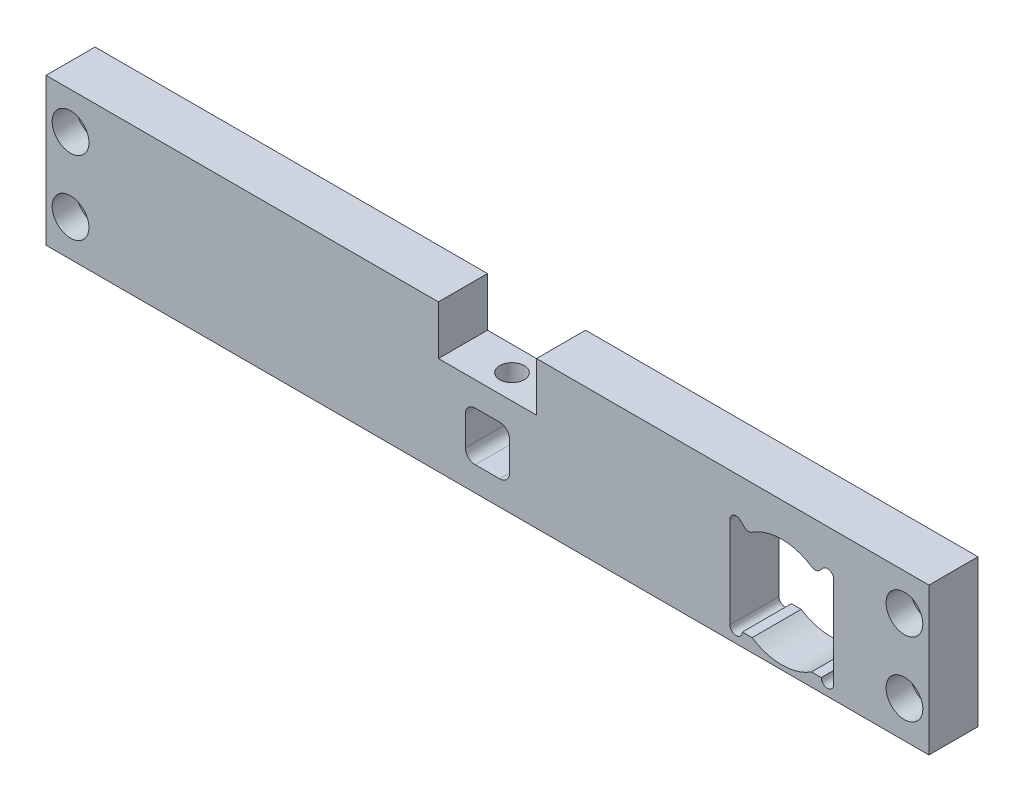
SolidWorks part; units mm, degrees
material "6061-T6 (SS)"
ref_plane "Front Plane" through (0, 0, 0) normal (0, 0, 1) x (1, 0, 0)
ref_plane "Top Plane" through (0, 0, 0) normal (0, 1, 0) x (1, 0, 0)
ref_plane "Right Plane" through (0, 0, 0) normal (1, 0, 0) x (0, 0, -1)
sketch "Sketch1" plane through (0, 0, 0) normal (0, 0, 1) x (1, 0, 0)
  line L1 (-190.5, -19.05) -> (38.1, -19.05)
  line L2 (-190.5, -19.05) -> (-190.5, 19.05)
  line L3 (-190.5, 19.05) -> (38.1, 19.05)
  line L4 (38.1, -19.05) -> (38.1, 19.05)
  line L5 (-190.5, -19.05) -> (38.1, 19.05) construction
  line L6 (-190.5, 19.05) -> (38.1, -19.05) construction
  line L7 (-190.5, 19.05) -> (38.1, 19.05)
  line L8 (-190.5, 19.05) -> (-190.5, -19.05)
  line L11 (-190.5, -19.05) -> (38.1, -19.05)
  line L12 (-190.5, -19.05) -> (-190.5, 19.05)
  line L15 (38.1, -19.05) -> (-190.5, -19.05)
  line L16 (38.1, -19.05) -> (38.1, 19.05)
  line L20 (38.1, -19.05) -> (38.1, 19.05)
  point P0 (0, 0)
  point P14 (-76.2, 0)
  dimension "D1" = 38.1
  dimension "D2" = 228.6
  dimension "D3" = 38.1
extrude "Boss-Extrude1" add sketch "Sketch1" along normal blind 12.7 contours L4 L3 L2 L1 region at (-76.2, 0, 0)
sketch "Sketch5" plane through (0, 0, 12.7) normal (0, 0, 1) x (1, 0, 0)
  line L0 (0, -3.81) -> (11.8187, 8.0087) construction
  line L1 (0, -3.81) -> (11.8187, -3.81) construction
  line L2 (0, -3.81) -> (0, 8.0087) construction
  line L3 (0, 8.0087) -> (11.8187, 8.0087) construction
  line L4 (11.8187, -3.81) -> (11.8187, 8.0087) construction
  line L5 (-10.6872, 9.1402) -> (-8.7721, 7.2252)
  line L6 (0, -3.81) -> (11.8187, -3.81) construction
  line L7 (0, -3.81) -> (0, -15.6287) construction
  line L8 (0, -15.6287) -> (11.8187, -15.6287) construction
  line L9 (11.8187, -3.81) -> (11.8187, -15.6287) construction
  line L10 (0, -3.81) -> (-11.8187, -3.81) construction
  line L11 (0, -3.81) -> (0, -15.6287) construction
  line L12 (0, -15.6287) -> (-11.8187, -15.6287) construction
  line L13 (-11.8187, -3.81) -> (-11.8187, -15.6287) construction
  line L14 (0, -3.81) -> (-11.8187, -3.81) construction
  line L15 (0, -3.81) -> (0, 8.0087) construction
  line L16 (0, 8.0087) -> (-11.8187, 8.0087) construction
  line L17 (-11.8187, -3.81) -> (-11.8187, 8.0087) construction
  line L18 (-13.4189, 8.0087) -> (-13.4189, -15.6287)
  line L19 (13.4189, 8.0087) -> (13.4189, -15.6287)
  line L20 (10.9269, 9.3374) -> (8.7958, 7.2063)
  line L21 (-13.4189, -15.6287) -> (-13.4189, -19.05)
  line L22 (-190.5, -19.05) -> (38.1, -19.05) construction
  line L23 (-13.4189, -19.05) -> (13.4189, -19.05)
  line L24 (13.4189, -19.05) -> (13.4189, -15.6287)
  line L25 (-10.2185, -15.6287) -> (-7.6839, -15.6287)
  line L26 (10.2185, -15.6287) -> (7.6839, -15.6287)
  circle A0 centre (0, -3.81) radius 14.097 construction
  circle A1 centre (11.8187, 8.0087) radius 1.6002
  circle A2 centre (-11.8187, 8.0087) radius 1.6002
  circle A3 centre (-11.8187, -15.6287) radius 1.6002
  circle A4 centre (11.8187, -15.6287) radius 1.6002
  arc A5 (-8.7721, 7.2252) -> (8.7958, 7.2063) centre (0, -3.81) cw
  arc A6 (-7.6839, -15.6287) -> (7.6839, -15.6287) centre (0, -3.81) ccw
  point P6 (9.9681, 6.1581)
  point P7 (10.6872, 6.8772)
  line M8 (-190.5, -19.05) -> (38.1, -19.05)
  dimension "D1" = 28.194
  dimension "D2" = 3.2004
  dimension "D3" = 1.017
  dimension "D4" = 45
  dimension "D5" = 45
  dimension "D6" = 15.24
extrude "Cut-Extrude4" cut sketch "Sketch5" against normal through all contours A5 L5 A2 L18 A3 L21 L24 A4 L19 A1 L20 M8 | A4 | A3 | A2 | A1 L20 region at (-0.0011, -3.8263, 12.7) region at (-11.8187, 8.0087, 12.7) region at (-11.8187, -15.6287, 12.7) region at (11.8205, 8.007, 12.7) region at (11.8187, -15.6287, 12.7)
fillet "Fillet1" radius 1.5875 2 edges at (8.7958, 7.2063, 6.35) (-8.7721, 7.2252, 6.35)
sketch "Sketch6" plane through (0, 0, 12.7) normal (0, 0, 1) x (1, 0, 0)
  line L0 (-190.5, 19.05) -> (38.1, 19.05) construction
  line L1 (-88.9, 19.05) -> (-63.5, 19.05)
  line L2 (-88.9, 19.05) -> (-88.9, 6.35)
  line L3 (-88.9, 6.35) -> (-63.5, 6.35)
  line L4 (-63.5, 19.05) -> (-63.5, 6.35)
  point P6 (-76.2, 6.35)
  point P7 (-76.2, 19.05)
  point P8 (-88.9, 19.05)
  dimension "D1" = 12.7
  dimension "D2" = 25.4
  dimension "D3" = 0
extrude "Cut-Extrude5" cut sketch "Sketch6" against normal through all
sketch "Sketch7" plane through (0, 0, 12.7) normal (0, 0, 1) x (1, 0, 0)
  line L0 (-88.9, 6.35) -> (-63.5, 6.35) construction
  line L1 (-81.915, -12.7) -> (-70.485, -12.7)
  line L2 (-81.915, -12.7) -> (-81.915, 0)
  line L3 (-81.915, 0) -> (-70.485, 0)
  line L4 (-70.485, -12.7) -> (-70.485, 0)
  line L5 (-190.5, -19.05) -> (38.1, -19.05) construction
  point P4 (-76.2, 6.35)
  point P5 (-76.2, 0)
  dimension "D1" = 11.43
  dimension "D2" = 6.35
  dimension "D3" = 6.35
extrude "Cut-Extrude6" cut sketch "Sketch7" against normal through all
sketch "Sketch8" plane through (0, 6.35, 0) normal (0, 1, 0) x (1, 0, 0)
  line L0 (-88.9, 0) -> (-63.5, 0) construction
  line L1 (-88.9, -12.7) -> (-63.5, -12.7) construction
  circle A0 centre (-76.2, -6.35) radius 3.175
  point P2 (-76.2, 0)
  point P3 (-76.2, -12.7)
  dimension "D1" = 6.35
  dimension "D2" = 6.35
extrude "Cut-Extrude7" cut sketch "Sketch8" against normal up to surface (6.35 mm away) up to face at (-76.2, 0, 6.35)
sketch "Sketch9" plane through (0, 0, 0) normal (0, 0, -1) x (-1, 0, 0)
  line L0 (-38.1, -19.05) -> (-38.1, 19.05) construction
  line L1 (-31.75, 9.525) -> (184.15, 9.525) construction
  line L2 (-31.75, 9.525) -> (-31.75, -9.525) construction
  line L3 (-31.75, -9.525) -> (184.15, -9.525) construction
  line L4 (184.15, 9.525) -> (184.15, -9.525) construction
  line L5 (190.5, -19.05) -> (190.5, 19.05) construction
  line L6 (190.5, 19.05) -> (88.9, 19.05) construction
  line L7 (190.5, -19.05) -> (-38.1, -19.05) construction
  circle A0 centre (-31.75, 9.525) radius 3.175
  circle A1 centre (-31.75, -9.525) radius 3.175
  circle A2 centre (184.15, 9.525) radius 3.175
  circle A3 centre (184.15, -9.525) radius 3.175
  dimension "D2" = 6.35
  dimension "D3" = 6.35
  dimension "D1" = 6.35
  dimension "D4" = 9.525
  dimension "D5" = 9.525
extrude "Cut-Extrude8" cut sketch "Sketch9" against normal through all
sketch "Sketch10" plane through (0, 0, 12.7) normal (0, 0, 1) x (1, 0, 0)
  circle A0 centre (-184.15, 9.525) radius 4.7625
  circle A1 centre (-184.15, -9.525) radius 4.7625
  circle A2 centre (31.75, 9.525) radius 4.7625
  circle A3 centre (31.75, -9.525) radius 4.7625
  dimension "D1" = 9.525
extrude "Cut-Extrude9" cut sketch "Sketch10" against normal blind 6.35
fillet "Fillet2" radius 2.54 4 edges at (-81.915, 0, 6.35) (-70.485, 0, 6.35) (-70.485, -12.7, 6.35) (-81.915, -12.7, 6.35)
